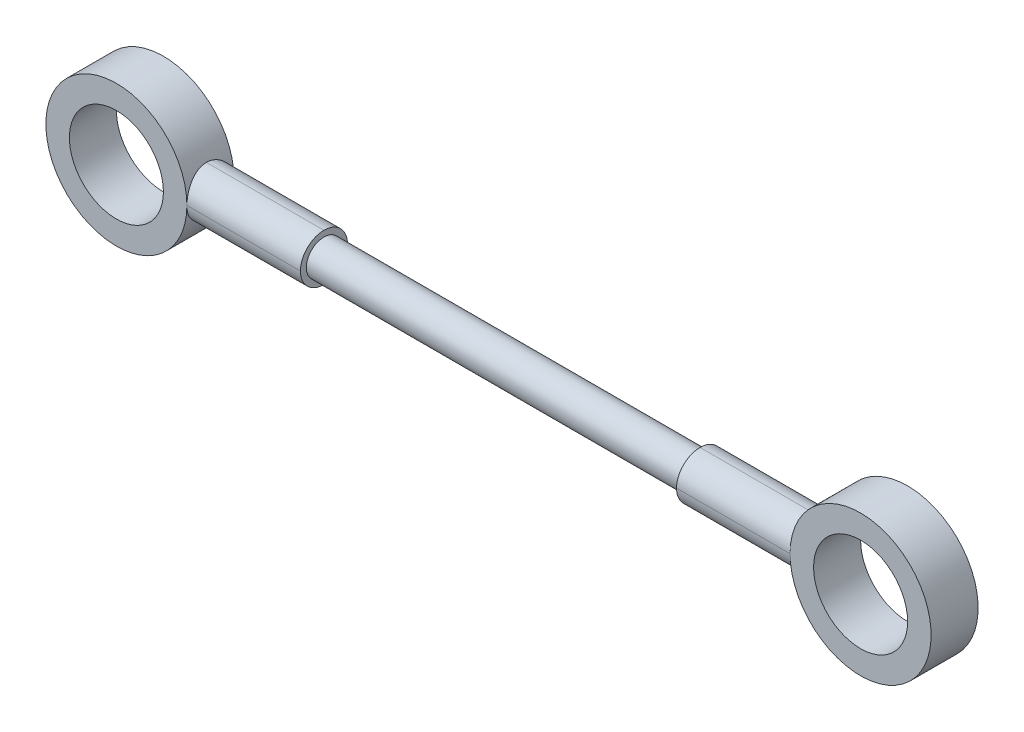
SolidWorks part; units mm, degrees
ref_plane "前视基准面" through (0, 0, 0) normal (0, 0, 1) x (1, 0, 0)
ref_plane "上视基准面" through (0, 0, 0) normal (0, 1, 0) x (1, 0, 0)
ref_plane "右视基准面" through (0, 0, 0) normal (1, 0, 0) x (0, 0, -1)
other "Configuration Table"
sketch "草图2" plane through (0, 0, 0) normal (0, 0, 1) x (1, 0, 0)
  line L0 (0, 0) -> (5, 0)
  line L1 (0, -2) -> (5, -2)
  line L2 (5, 0) -> (5, -2)
  arc A0 (0, 0) -> (0, -2) centre (-2.8284, -1) ccw
  dimension "D3" = 3
  dimension "D1" = 5
  dimension "D2" = 2
  dimension "D4" = 5
extrude "凸台-拉伸1" add sketch "草图2" along normal blind 2
sketch "草图3" plane through (5, 0, 0) normal (1, 0, 0) x (0, 0, -1)
  circle A0 centre (-1, -1) radius 0.75
  dimension "D1" = 1.5
extrude "凸台-拉伸2" add sketch "草图3" along normal blind 20
ref_plane "基准面1" through (13, 0, 0) normal (1, 0, 0) x (0, 0, -1)
sketch "草图6" plane through (0, 0, 2) normal (0, 0, 1) x (1, 0, 0)
  circle A0 centre (-2.8284, -1) radius 2
  dimension "D1" = 4
extrude "切除-拉伸1" cut sketch "草图6" against normal blind 20
mirror "镜向9" about plane through (13, 0, 0) normal (1, 0, 0) of "凸台-拉伸1"
sketch "草图7" plane through (0, 0, 0) normal (0, 0, -1) x (-1, 0, 0)
  circle A0 centre (-28.8284, -1) radius 2
  dimension "D1" = 4
extrude "切除-拉伸2" cut sketch "草图7" against normal blind 20
ref_plane "基准面2" through (0, 0, 1) normal (0, 0, 1) x (1, 0, 0)
sketch "草图8" plane through (0, 0, 1) normal (0, 0, 1) x (1, 0, 0)
  circle A0 centre (-2.8284, -1) radius 2
  circle A1 centre (28.8284, -1) radius 2
fillet "圆角2" radius 1 4 edges at (2.5, -2, 2) (2.5, -2, 0) (2.5, 0, 0) (2.5, 0, 2)
fillet "圆角3" radius 1 4 edges at (23.5, -2, 2) (23.5, -2, 0) (23.5, 0, 0) (23.5, 0, 2)
